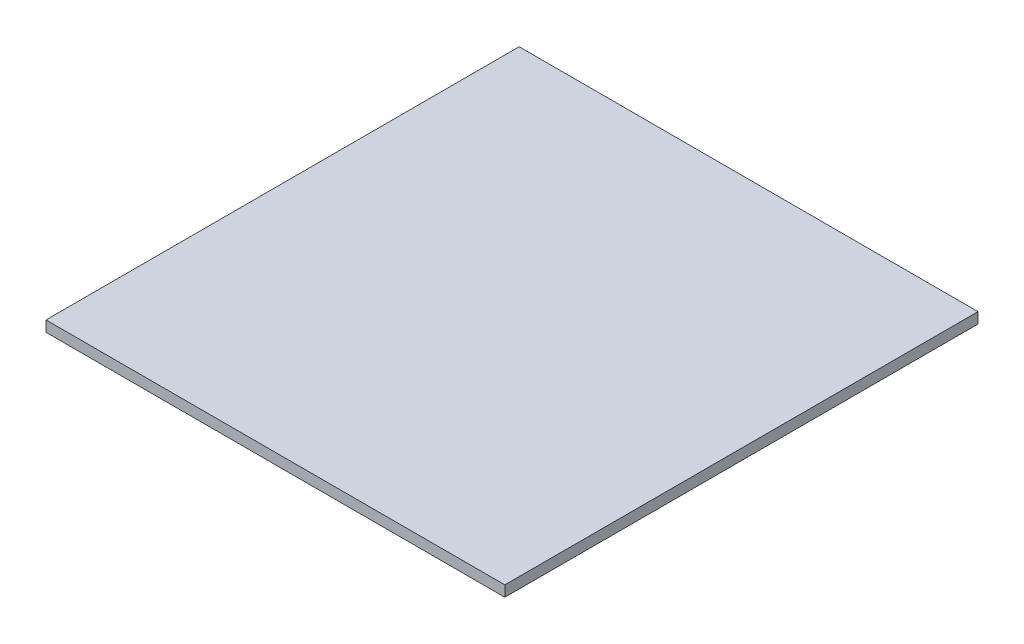
SolidWorks part; units mm, degrees
material "Pine"
ref_plane "Front Plane" through (0, 0, 0) normal (0, 0, 1) x (1, 0, 0)
ref_plane "Top Plane" through (0, 0, 0) normal (0, 1, 0) x (1, 0, 0)
ref_plane "Right Plane" through (0, 0, 0) normal (1, 0, 0) x (0, 0, -1)
sketch "Sketch1" plane through (0, 0, 0) normal (0, 1, 0) x (1, 0, 0)
  line L0 (-97.5279, 759.6989) -> (-97.5279, -78.5011)
  line L1 (-97.5279, -78.5011) -> (715.2721, -78.5011)
  line L2 (-97.5279, 759.6989) -> (715.2721, 759.6989)
  line L3 (715.2721, -78.5011) -> (715.2721, 759.6989)
extrude "Boss-Extrude1" add sketch "Sketch1" along normal blind 19.05
